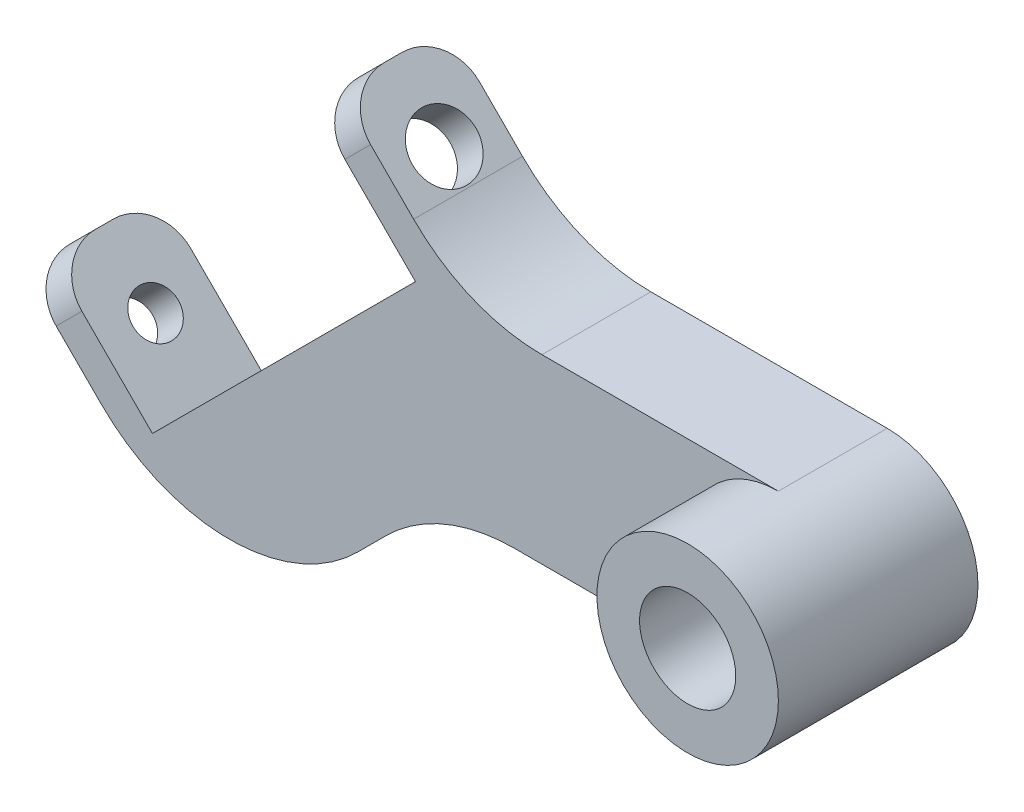
SolidWorks part; units mm, degrees
ref_plane "Piano frontale" through (0, 0, 0) normal (0, 0, 1) x (1, 0, 0)
ref_plane "Piano superiore" through (0, 0, 0) normal (0, 1, 0) x (1, 0, 0)
ref_plane "Piano destro" through (0, 0, 0) normal (1, 0, 0) x (0, 0, -1)
sketch "Schizzo1" plane through (0, 0, 0) normal (0, 0, 1) x (1, 0, 0)
  line L0 (0, 0) -> (-20, 0)
  line L1 (-20, 0) -> (-10, 10)
  line L2 (-10, 10) -> (10, 10)
  line L4 (10, 0) -> (0, 0)
  arc A0 (10, 0) -> (10, 10) centre (10, 5) ccw
  dimension "D6" = 10
  dimension "D1" = 20
  dimension "D2" = 10
  dimension "D3" = 10
  dimension "D4" = 0
  dimension "D5" = 20
extrude "Estrusione-Estrusione1" add sketch "Schizzo1" along normal blind 6 contours L2 A0 L4 L0 L1
sketch "Schizzo3" plane through (0, 0, 6) normal (0, 0, 1) x (1, 0, 0)
  arc A0 (10, 0) -> (10, 10) centre (10, 5) ccw construction
  arc A1 (10, 0) -> (10, 10) centre (10, 5) ccw construction
  circle A2 centre (10, 5) radius 5
  circle A3 centre (10, 5) radius 2.65
  dimension "D1" = 5.3
extrude "Estrusione-Estrusione3" add sketch "Schizzo3" along normal blind 5
sketch "Schizzo4" plane through (0, 0, 6) normal (0, 0, 1) x (1, 0, 0)
  line L0 (-10, 10) -> (-16.0795, 16.0795)
  line L1 (-20, 0) -> (-10, 10) construction
ref_plane "Piano1" through (0, 0, 0) normal (0.7071, 0.7071, 0) x (-0.7071, 0.7071, 0)
sketch "Schizzo5" plane through (0, 0, 0) normal (0.7071, 0.7071, 0) x (-0.7071, 0.7071, 0)
  line L0 (14.1421, 3) -> (18.1421, 3)
  line L1 (14.1421, 6) -> (14.1421, 0) construction
  circle A0 centre (18.1421, 3) radius 0.925
  dimension "D2" = 1.85
  dimension "D1" = 4
extrude "Estrusione-Estrusione4" add sketch "Schizzo5" against normal blind 20 separate body contours A0 region at (-12.8284, 12.8284, 2.1012)
sketch "Schizzo12" plane through (0, 0, 0) normal (0.7071, 0.7071, 0) x (-0.7071, 0.7071, 0)
  line L0 (14.1421, 0) -> (0, 0) construction
  line L1 (14.1421, 6) -> (22.1421, 6)
  line L2 (14.1421, 6) -> (14.1421, 0)
  line L3 (14.1421, 0) -> (22.1421, 0)
  line L4 (22.1421, 6) -> (22.1421, 0)
  dimension "D1" = 8
extrude "Estrusione-Estrusione6" add sketch "Schizzo12" along normal blind 2
sketch "Schizzo13" plane through (-10, 10, 0) normal (0.7071, -0.7071, 0) x (0, 0, -1)
  line L4 (-6, 0) -> (0, 0)
  line L5 (0, 0) -> (0, 2)
  line L6 (0, 2) -> (-6, 2)
  line L7 (-6, 2) -> (-6, 0)
  line L8 (-6, 0) -> (0, 0)
  line L9 (0, 0) -> (0, 2)
  line L10 (0, 2) -> (-6, 2)
  line L11 (-6, 2) -> (-6, 0)
  dimension "D1" = 0
extrude "Estrusione-Estrusione7" add sketch "Schizzo13" along normal blind 3
fillet "Raccordo2" radius 2.5 2 edges at (-14.9497, 16.364, 0) (-14.9497, 16.364, 6)
sketch "Schizzo14" plane through (1.4142, 1.4142, 0) normal (0.7071, 0.7071, 0) x (0, 0, -1)
  circle A0 centre (-3, 18.1421) radius 1.75
  circle A1 centre (-3, 18.1421) radius 0.925
  circle A2 centre (-3, 18.1421) radius 0.925
  dimension "D2" = 3.5
  dimension "D1" = 0
extrude "Taglio-Estrusione7" cut sketch "Schizzo14" against normal blind 25 contours A2 | A0 A2 | A2 | A0 region at (-11.4142, 14.2426, 4.7005) region at (-11.4142, 14.2426, 3)
sketch "Schizzo15" plane through (0, 0, 0) normal (-0.7071, -0.7071, 0) x (0, 0, 1)
  line L0 (0, 14.1421) -> (0, 19.6421) construction
  line L1 (6, 14.1421) -> (0, 14.1421)
  line L2 (6, 14.1421) -> (6, 6.1421)
  line L3 (6, 6.1421) -> (0, 6.1421)
  line L4 (0, 14.1421) -> (0, 6.1421)
  dimension "D1" = 8
extrude "Estrusione-Estrusione8" add sketch "Schizzo15" along normal blind 22.5
sketch "Schizzo16" plane through (-10, 10, 0) normal (-0.7071, 0.7071, 0) x (0, 0, 1)
  line L0 (0, -22.5) -> (0, 0) construction
  line L1 (6, -22.5) -> (0, -22.5)
  line L2 (6, -22.5) -> (6, -20.5)
  line L3 (6, -20.5) -> (0, -20.5)
  line L4 (0, -22.5) -> (0, -20.5)
  dimension "D1" = 2
extrude "Estrusione-Estrusione9" add sketch "Schizzo16" along normal up to vertex up to point (-15.6569, 15.6569, 2.5)
sketch "Schizzo17" plane through (-15.9099, -15.9099, 0) normal (-0.7071, -0.7071, 0) x (0, 0, 1)
  circle A0 centre (3, 18.1421) radius 1.75 construction
  circle A1 centre (3, 18.1421) radius 1.75
  circle A2 centre (3, 18.1421) radius 1.25
  dimension "D1" = 2.5
extrude "Taglio-Estrusione8" cut sketch "Schizzo17" against normal blind 25 contours A2
fillet "Raccordo3" radius 10 1 edges at (-20.253, -11.5668, 3)
fillet "Raccordo4" radius 10 1 edges at (-8.6863, 0, 3)
fillet "Raccordo5" radius 10 1 edges at (-7.1716, 10, 3)
fillet "Raccordo6" radius 2.5 2 edges at (-30.8597, 0.4541, 0) (-30.8597, 0.4541, 6)
sketch "Schizzo18" plane through (0, 0, 6) normal (0, 0, 1) x (1, 0, 0)
  circle A0 centre (10, 5) radius 1.75
  dimension "D1" = 3.5
extrude "Taglio-Estrusione9" cut sketch "Schizzo18" against normal through all
